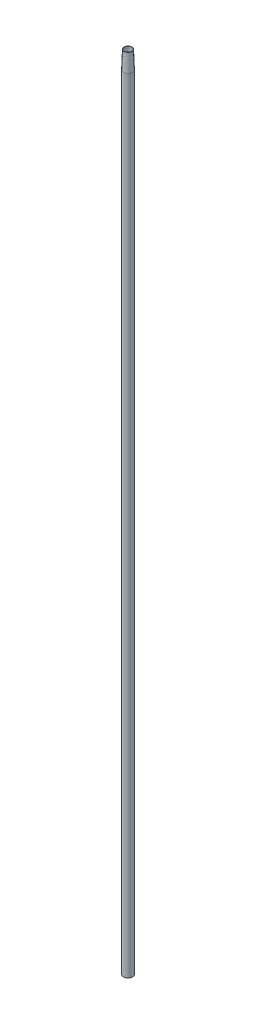
SolidWorks part; units mm, degrees
ref_plane "Front Plane" through (0, 0, 0) normal (0, 0, 1) x (1, 0, 0)
ref_plane "Top Plane" through (0, 0, 0) normal (0, 1, 0) x (1, 0, 0)
ref_plane "Right Plane" through (0, 0, 0) normal (1, 0, 0) x (0, 0, -1)
sketch "Sketch1" plane through (0, 0, 0) normal (0, 1, 0) x (1, 0, 0)
  circle A0 centre (0, 0) radius 2.555
  circle A1 centre (0, 0) radius 2.055
  dimension "D1" = 0.5
  dimension "D2" = 5.11
extrude "Boss-Extrude1" add sketch "Sketch1" along normal blind 450
chamfer "Chamfer1" distance 10 angle 2 1 edges at (0, 450, 2.555) first distance on face at (0, 450, 2.555)
